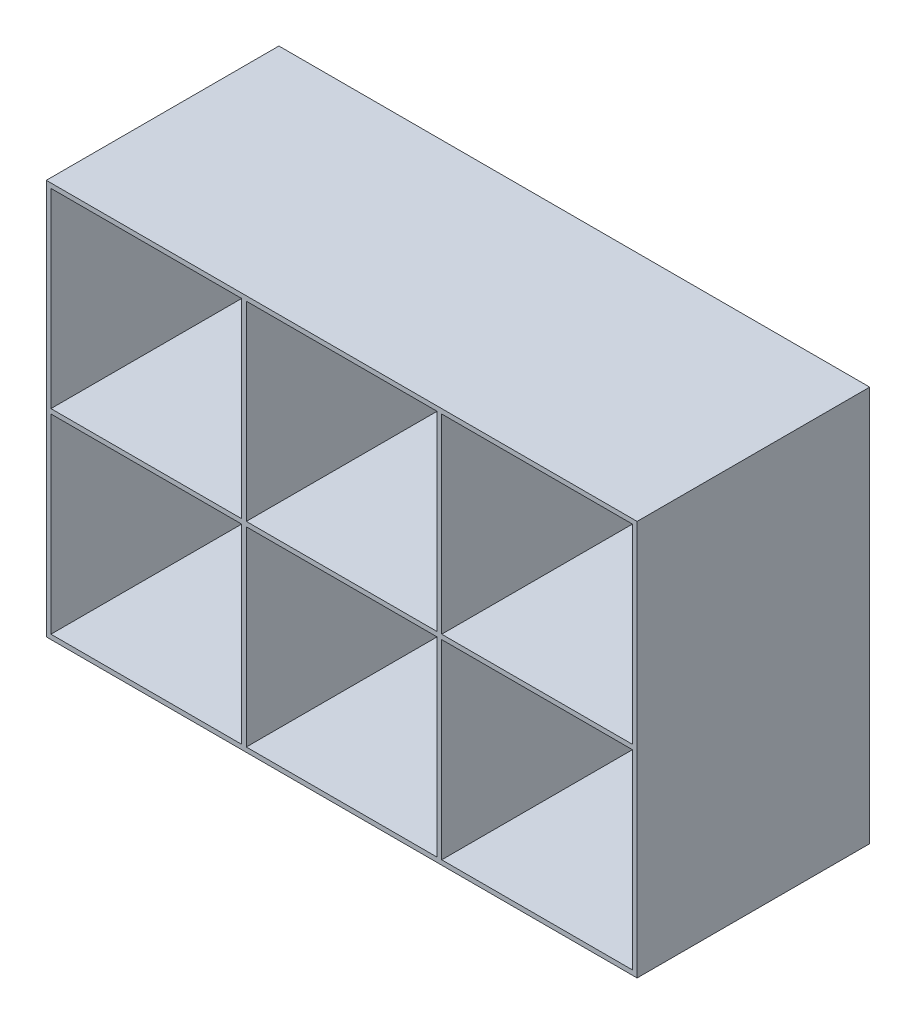
SolidWorks part; units mm, degrees
ref_plane "正面" through (0, 0, 0) normal (0, 0, 1) x (1, 0, 0)
ref_plane "平面" through (0, 0, 0) normal (0, 1, 0) x (1, 0, 0)
ref_plane "右側面" through (0, 0, 0) normal (1, 0, 0) x (0, 0, -1)
sketch "ｽｹｯﾁ1" plane through (0, 0, 0) normal (0, 0, 1) x (1, 0, 0)
  line L0 (-63.8848, 38.674) -> (-63.8848, 18.174)
  line L1 (-84.8848, 38.674) -> (-64.3848, 38.674)
  line L2 (-84.8848, 38.674) -> (-84.8848, 18.174)
  line L3 (-84.8848, 18.174) -> (-64.3848, 18.174)
  line L4 (-64.3848, 38.674) -> (-64.3848, 18.174)
  line L5 (-63.8848, 38.674) -> (-43.3848, 38.674)
  line L6 (-43.3848, 38.674) -> (-43.3848, 18.174)
  line L7 (-63.8848, 18.174) -> (-43.3848, 18.174)
  line L8 (-42.8848, 38.674) -> (-42.8848, 18.174)
  line L9 (-42.8848, 38.674) -> (-22.3848, 38.674)
  line L10 (-22.3848, 38.674) -> (-22.3848, 18.174)
  line L11 (-42.8848, 18.174) -> (-22.3848, 18.174)
  line L12 (-63.8848, 59.674) -> (-63.8848, 39.174)
  line L13 (-63.8848, 39.174) -> (-43.3848, 39.174)
  line L14 (-43.3848, 59.674) -> (-43.3848, 39.174)
  line L15 (-63.8848, 59.674) -> (-43.3848, 59.674)
  line L16 (-42.8848, 59.674) -> (-42.8848, 39.174)
  line L17 (-42.8848, 39.174) -> (-22.3848, 39.174)
  line L18 (-22.3848, 59.674) -> (-22.3848, 39.174)
  line L19 (-42.8848, 59.674) -> (-22.3848, 59.674)
  line L20 (-84.8848, 59.674) -> (-84.8848, 39.174)
  line L21 (-84.8848, 59.674) -> (-64.3848, 59.674)
  line L22 (-64.3848, 59.674) -> (-64.3848, 39.174)
  line L23 (-84.8848, 39.174) -> (-64.3848, 39.174)
  line L25 (-85.3848, 60.174) -> (-21.8848, 60.174)
  line L26 (-85.3848, 60.174) -> (-85.3848, 17.674)
  line L27 (-85.3848, 17.674) -> (-21.8848, 17.674)
  line L28 (-21.8848, 60.174) -> (-21.8848, 17.674)
  dimension "D1" = 20.5
  dimension "D2" = 20.5
  dimension "D5" = 0.5
  dimension "D6" = 0.5
  dimension "D7" = 0.5
  dimension "D8" = 0.5
  dimension "D9" = 0.5
  dimension "D10" = 0.5
  dimension "D3" = 3
  dimension "D4" = 2
extrude "ﾎﾞｽ - 押し出し1" add sketch "ｽｹｯﾁ1" along normal blind 25
